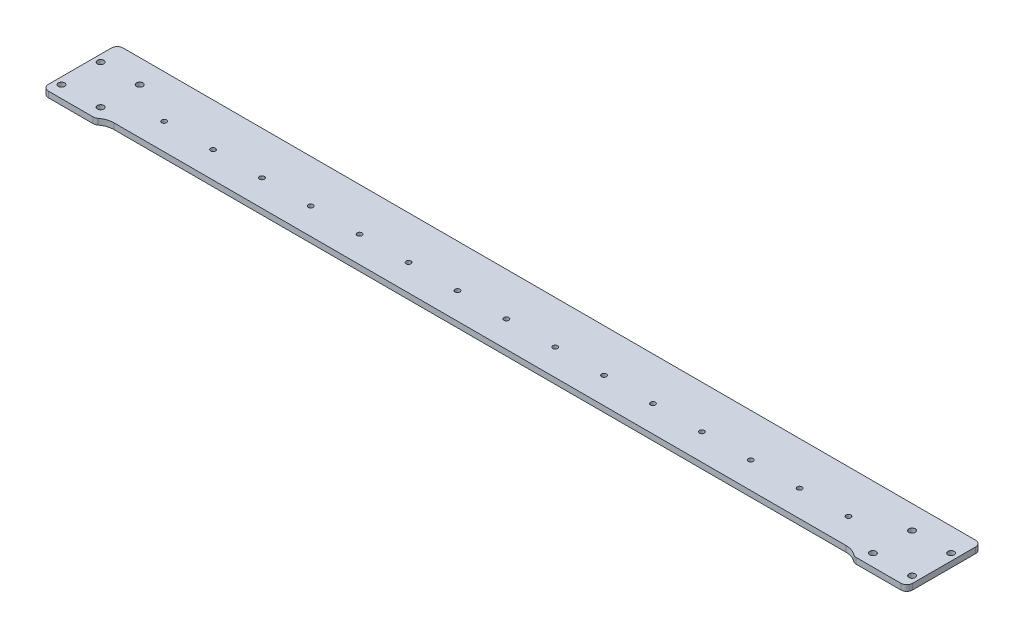
SolidWorks part; units mm, degrees
material "AISI 1045 Steel, cold drawn"
ref_plane "Front Plane" through (0, 0, 0) normal (0, 0, 1) x (1, 0, 0)
ref_plane "Top Plane" through (0, 0, 0) normal (0, 1, 0) x (1, 0, 0)
ref_plane "Right Plane" through (0, 0, 0) normal (1, 0, 0) x (0, 0, -1)
sketch "Sketch1" plane through (0, 0, 0) normal (0, 1, 0) x (1, 0, 0)
  line L0 (0, 0) -> (194, 0)
  line L1 (194, 0) -> (194, -2.7)
  line L2 (194, -2.7) -> (221, -2.7)
  line L3 (221, -2.7) -> (221, 29.7)
  line L4 (221, 29.7) -> (0, 29.7) construction
  line L7 (0, 0) -> (0, 29.7)
  line L8 (221, 13.5) -> (0, 13.5) construction
  line L9 (221, 29.7) -> (221, 35.5)
  line L10 (221, 35.5) -> (0, 35.5)
  line L11 (0, 35.5) -> (0, 29.7)
  dimension "D1" = 194
  dimension "D2" = 27
  dimension "D3" = 29.7
  dimension "D4" = 32.4
  dimension "D5" = 22
extrude "Boss-Extrude1" add sketch "Sketch1" along normal blind 3
hole_wizard "M3 Clearance Hole1" positions "Sketch2" profile "Sketch3" hole size "M3" standard "ANSI Metric" end condition through all
sketch "Sketch2" plane through (0, 3, 0) normal (0, 1, 0) x (1, 0, 0)
  line L1 (217.5, 3.5) -> (197.5, 3.5)
  line L2 (217.5, 3.5) -> (217.5, 23.5)
  line L3 (217.5, 23.5) -> (197.5, 23.5)
  line L4 (197.5, 3.5) -> (197.5, 23.5)
  line L5 (217.5, 3.5) -> (197.5, 23.5) construction
  line L6 (217.5, 23.5) -> (197.5, 3.5) construction
  line L10 (207.5, 13.5) -> (207.5, -2.7) construction
  line L13 (194, -2.7) -> (221, -2.7) construction
  line L17 (0, 0) -> (194, 0) construction
  point P2 (197.5, 23.5)
  point P35 (217.5, 3.5)
  point P36 (217.5, 23.5)
  point P37 (197.5, 3.5)
  dimension "D1" = 20
  dimension "D2" = 13.5
sketch "Sketch3" plane through (197.5, 3, -23.5) normal (1, 0, 0) x (0, 0, 1)
  line L0 (0, 0) -> (0, 3)
  line L1 (0, 3) -> (1.6, 3)
  line L2 (1.6, 3) -> (1.6, 0.025)
  line L3 (1.6, 0.025) -> (1.625, 0)
  line L5 (1.625, 0) -> (0, 0)
  line L6 (-1.6, 0.025) -> (-1.625, 0) construction
  line L11 (0, -6.35) -> (0, 107.95) construction
  dimension "Thru Hole Dia." = 3.2
  dimension "Thru Hole Depth" = 3
  dimension "Near C'Sink Dia." = 3.25
  dimension "Near C'Sink Angle" = 90
fillet "Fillet1" radius 10 1 edges at (194, 1.5, 0)
fillet "Fillet2" radius 3 3 edges at (221, 1.5, 2.7) (194, 1.5, 2.7) (221, 1.5, -35.5)
mirror "Mirror1" about plane through (0, 3, -35.5) normal (1, 0, 0) of bodies 103
hole_wizard "Tap Drill for M3x0.5 Tap2" positions "Sketch6" profile "Sketch7" hole size "M3x0.5" standard "ANSI Metric" end condition through all
sketch "Sketch6" plane through (0, 0, 0) normal (0, -1, 0) x (-1, 0, 0)
  point P0 (-175, 13.5)
sketch "Sketch7" plane through (175, 0, -13.5) normal (1, 0, 0) x (0, 0, -1)
  line L0 (0, 0) -> (0, 3)
  line L1 (0, 3) -> (1.25, 3)
  line L2 (1.25, 3) -> (1.25, 0.025)
  line L3 (1.25, 0.025) -> (1.275, 0)
  line L5 (1.275, 0) -> (0, 0)
  line L6 (-1.25, 0.025) -> (-1.275, 0) construction
  line L11 (0, -6.35) -> (0, 107.95) construction
  dimension "Thru Hole Dia." = 2.5
  dimension "Thru Hole Depth" = 3
  dimension "Near C'Sink Dia." = 2.55
  dimension "Near C'Sink Angle" = 90
pattern_linear "LPattern1" count 15 spacing 25 along (-1, 0, 0) of "Tap Drill for M3x0.5 Tap2"
